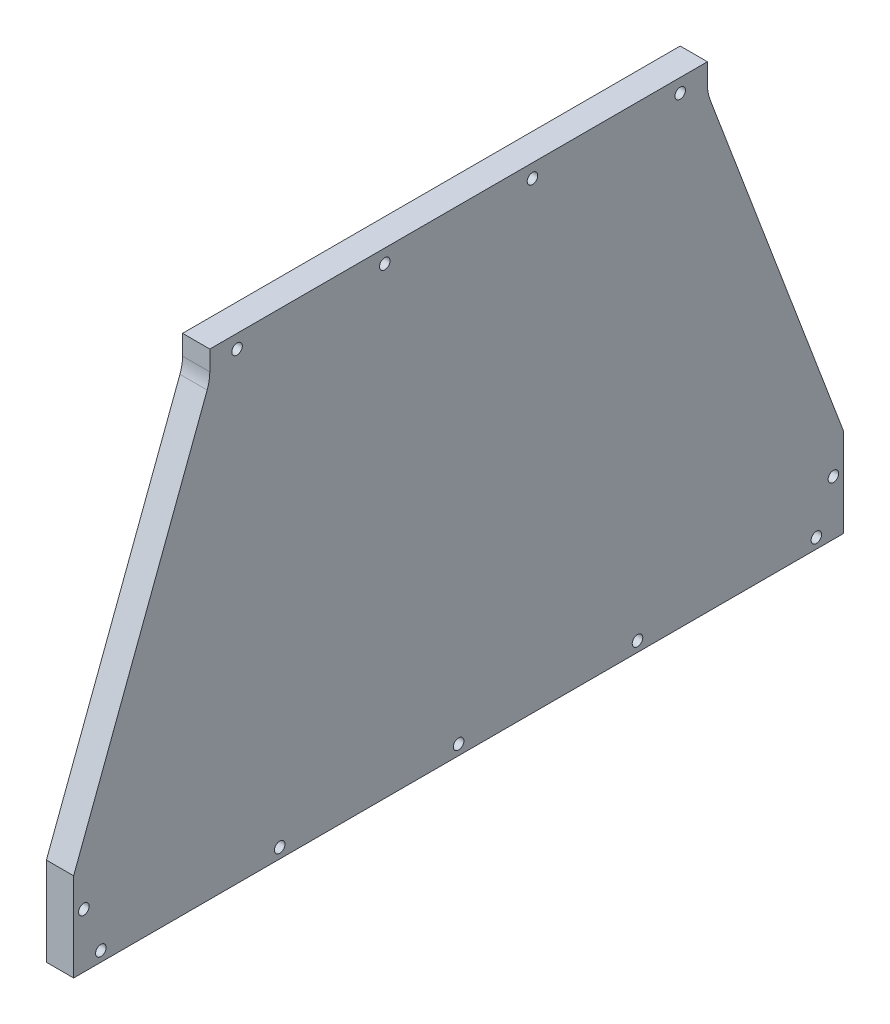
SolidWorks part; units mm, degrees
material "PC High Viscosity"
ref_plane "Front Plane" through (0, 0, 0) normal (0, 0, 1) x (1, 0, 0)
ref_plane "Top Plane" through (0, 0, 0) normal (0, 1, 0) x (1, 0, 0)
ref_plane "Right Plane" through (0, 0, 0) normal (1, 0, 0) x (0, 0, -1)
sketch "Sketch1" plane through (-152.4, 0, 0) normal (-1, 0, 0) x (0, 0, 1)
  line L2 (179.525, -30.525) -> (179.525, 10.75)
  line L3 (179.525, 10.75) -> (116.025, 179.025)
  line L4 (116.025, 179.025) -> (-116.025, 179.025) construction
  line L5 (-116.025, 179.025) -> (-179.525, 10.75)
  line L9 (-116.025, 179.025) -> (-116.025, 191.725)
  line L10 (-116.025, 191.725) -> (116.025, 191.725)
  line L11 (116.025, 191.725) -> (116.025, 179.025)
  line L12 (71.3064, 110.2997) -> (71.3064, 107.6694)
  line L13 (71.3064, 110.2997) -> (71.3064, 107.6694) construction
  line L14 (71.3064, 107.6694) -> (83.0865, 85.1176)
  line L15 (71.3064, 107.6694) -> (83.0865, 85.1176) construction
  line L16 (83.0865, 85.1176) -> (85.1422, 81.1821)
  line L17 (83.0865, 85.1176) -> (85.1422, 81.1821) construction
  line L18 (88.7026, 79.025) -> (105.7742, 79.025)
  line L19 (88.7026, 79.025) -> (105.7742, 79.025) construction
  line L20 (105.7742, 55.4812) -> (88.7026, 55.4812)
  line L21 (105.7742, 55.4812) -> (88.7026, 55.4812) construction
  line L22 (85.1422, 53.3241) -> (83.0865, 49.3886)
  line L23 (85.1422, 53.3241) -> (83.0865, 49.3886) construction
  line L24 (83.0865, 49.3886) -> (71.3064, 26.8368)
  line L25 (83.0865, 49.3886) -> (71.3064, 26.8368) construction
  line L26 (71.3064, 26.8368) -> (71.3064, 24.2065)
  line L27 (71.3064, 26.8368) -> (71.3064, 24.2065) construction
  line L28 (66.4936, 18.7481) -> (34.9092, 18.7481)
  line L29 (66.4936, 18.7481) -> (34.9092, 18.7481) construction
  line L30 (34.9092, 18.7481) -> (32.2596, 20.2319)
  line L31 (34.9092, 18.7481) -> (32.2596, 20.2319) construction
  line L32 (32.2596, 20.2319) -> (24.473, 20.2319)
  line L33 (32.2596, 20.2319) -> (24.473, 20.2319) construction
  line L34 (24.473, 20.2319) -> (24.473, 19.2124)
  line L35 (24.473, 20.2319) -> (24.473, 19.2124) construction
  line L36 (24.473, 19.2124) -> (-24.6855, 19.2124)
  line L37 (24.473, 19.2124) -> (-24.6855, 19.2124) construction
  line L38 (-24.6855, 19.2124) -> (-26.36, 20.1501)
  line L39 (-24.6855, 19.2124) -> (-26.36, 20.1501) construction
  line L40 (-26.36, 20.1501) -> (-48.784, 20.1501)
  line L41 (-26.36, 20.1501) -> (-48.784, 20.1501) construction
  line L42 (-48.784, 20.1501) -> (-58.9234, 27.7663)
  line L43 (-48.784, 20.1501) -> (-58.9234, 27.7663) construction
  line L44 (-58.9234, 27.7663) -> (-60.282, 27.7663)
  line L45 (-58.9234, 27.7663) -> (-60.282, 27.7663) construction
  line L46 (-60.282, 27.7663) -> (-60.4466, 33.2204)
  line L47 (-60.282, 27.7663) -> (-60.4466, 33.2204) construction
  line L48 (-60.4466, 33.2204) -> (-66.7945, 33.2204)
  line L49 (-60.4466, 33.2204) -> (-66.7945, 33.2204) construction
  line L50 (-66.7945, 33.2204) -> (-66.7945, 34.9391)
  line L51 (-66.7945, 33.2204) -> (-66.7945, 34.9391) construction
  line L52 (-109.7529, 42.6097) -> (-109.7529, 91.8965)
  line L53 (-109.7529, 42.6097) -> (-109.7529, 91.8965) construction
  line L54 (-66.7945, 99.5665) -> (-66.7945, 101.2858)
  line L55 (-66.7945, 99.5665) -> (-66.7945, 101.2858) construction
  line L56 (-66.7945, 101.2858) -> (-60.4466, 101.2858)
  line L57 (-66.7945, 101.2858) -> (-60.4466, 101.2858) construction
  line L58 (-60.4466, 101.2858) -> (-60.282, 106.7399)
  line L59 (-60.4466, 101.2858) -> (-60.282, 106.7399) construction
  line L60 (-60.282, 106.7399) -> (-58.9234, 106.7399)
  line L61 (-60.282, 106.7399) -> (-58.9234, 106.7399) construction
  line L62 (-58.9234, 106.7399) -> (-48.784, 114.3561)
  line L63 (-58.9234, 106.7399) -> (-48.784, 114.3561) construction
  line L64 (-48.784, 114.3561) -> (-26.36, 114.3561)
  line L65 (-48.784, 114.3561) -> (-26.36, 114.3561) construction
  line L66 (-26.36, 114.3561) -> (-24.6855, 115.2938)
  line L67 (-26.36, 114.3561) -> (-24.6855, 115.2938) construction
  line L68 (-24.6855, 115.2938) -> (24.473, 115.2938)
  line L69 (-24.6855, 115.2938) -> (24.473, 115.2938) construction
  line L70 (24.473, 115.2938) -> (24.473, 114.2743)
  line L71 (24.473, 115.2938) -> (24.473, 114.2743) construction
  line L72 (24.473, 114.2743) -> (32.2596, 114.2743)
  line L73 (24.473, 114.2743) -> (32.2596, 114.2743) construction
  line L74 (32.2596, 114.2743) -> (34.9092, 115.7581)
  line L75 (32.2596, 114.2743) -> (34.9092, 115.7581) construction
  line L76 (34.9092, 115.7581) -> (66.4936, 115.7581)
  line L77 (34.9092, 115.7581) -> (66.4936, 115.7581) construction
  line L79 (179.525, -30.525) -> (-179.525, -30.525) construction
  line L80 (179.525, -30.525) -> (-179.525, -30.525)
  line L81 (-179.525, -30.525) -> (-179.525, 10.75)
  arc A0 (85.1422, 81.1821) -> (88.7026, 79.025) centre (88.7026, 83.0419) ccw
  arc A1 (85.1422, 81.1821) -> (88.7026, 79.025) centre (88.7026, 83.0419) ccw construction
  arc A2 (108.4945, 77.1118) -> (105.7742, 79.025) centre (105.7742, 76.1345) ccw
  arc A3 (108.4945, 77.1118) -> (105.7742, 79.025) centre (105.7742, 76.1345) ccw construction
  arc A4 (108.4945, 57.3944) -> (108.4945, 77.1118) centre (81.0531, 67.2531) ccw
  arc A5 (108.4945, 57.3944) -> (108.4945, 77.1118) centre (81.0531, 67.2531) ccw construction
  arc A6 (105.7742, 55.4812) -> (108.4945, 57.3944) centre (105.7742, 58.3717) ccw
  arc A7 (105.7742, 55.4812) -> (108.4945, 57.3944) centre (105.7742, 58.3717) ccw construction
  arc A8 (88.7026, 55.4812) -> (85.1422, 53.3241) centre (88.7026, 51.4644) ccw
  arc A9 (88.7026, 55.4812) -> (85.1422, 53.3241) centre (88.7026, 51.4644) ccw construction
  arc A10 (66.4936, 18.7481) -> (71.3064, 24.2065) centre (65.8047, 24.2065) ccw
  arc A11 (66.4936, 18.7481) -> (71.3064, 24.2065) centre (65.8047, 24.2065) ccw construction
  arc A12 (71.3064, 110.2997) -> (66.4936, 115.7581) centre (65.8047, 110.2997) ccw
  arc A13 (71.3064, 110.2997) -> (66.4936, 115.7581) centre (65.8047, 110.2997) ccw construction
  spline S0 degree 3 poles (-4.313, -1962.4963) (19.5421, 71.4299) (-25.3598, 33.5673) (-69.9826, 35.0151) (-72.2561, 35.1637) (-74.9774, 35.4287) (-80.4046, 36.0971) (-247.0965, 65.1595) (-376.3581, 268.4403) (-855.0908, -1792.3669) knots -2.937522 -2.937522 -2.937522 -2.937522 0.03125 0.0625 0.125 0.1875 0.25 0.5 11.786531 11.786531 11.786531 11.786531 only from (-66.7945, 34.9391) to (-109.7529, 42.6097)
  spline S1 degree 3 poles (-66.7945, 34.9391) (-67.2501, 34.9435) (-68.1613, 34.956) (-69.9826, 35.0151) (-72.2561, 35.1637) (-74.9774, 35.4287) (-80.4046, 36.0971) (-92.0812, 38.1329) (-102.7052, 40.749) (-109.7529, 42.6097) knots 0 0 0 0 0.03125 0.0625 0.125 0.1875 0.25 0.5 1 1 1 1 construction
  spline S2 degree 3 poles (-855.0104, 1926.8665) (-376.3436, -133.9191) (-247.0872, 69.3486) (-80.4046, 98.4091) (-74.9775, 99.0775) (-72.2562, 99.3426) (-69.9826, 99.4913) (-25.4887, 100.9281) (19.281, 62.7855) (-4.2393, 2096.9342) knots -10.785888 -10.785888 -10.785888 -10.785888 0.499999 0.749999 0.812499 0.875 0.9375 0.96875 3.928669 3.928669 3.928669 3.928669 only from (-109.7529, 91.8965) to (-66.7945, 99.5665)
  spline S3 degree 3 poles (-109.7529, 91.8965) (-102.7052, 93.7572) (-92.0812, 96.3733) (-80.4046, 98.4091) (-74.9775, 99.0775) (-72.2562, 99.3426) (-69.9826, 99.4913) (-68.1613, 99.5501) (-67.2501, 99.5623) (-66.7945, 99.5665) knots 0 0 0 0 0.499999 0.749999 0.812499 0.875 0.9375 0.96875 1 1 1 1 construction
  dimension "D1" = 12.7
  dimension "D2" = 222.25
  dimension "D3" = 63.5
  dimension "D4" = 41.275
  dimension "D5" = 63.7312
extrude "Boss-Extrude1" add sketch "Sketch1" along normal blind 12.7
fillet "Fillet1" radius 19.05 2 edges at (-158.75, 179.025, -116.025) (-158.75, 179.025, 116.025)
hole_wizard "#10 (0.1935) Diameter Hole1" positions "Sketch2" profile "Sketch3" hole size "#10" standard "ANSI Inch" end condition through all
sketch "Sketch2" plane through (-165.1, 0, 0) normal (-1, 0, 0) x (0, 0, 1)
  line L1 (-103.325, 185.375) -> (-34.4417, 185.375) construction
  line L2 (-34.4417, 185.375) -> (34.4417, 185.375) construction
  line L3 (34.4417, 185.375) -> (103.325, 185.375) construction
  line L5 (166.825, -25.7625) -> (83.4125, -25.7625) construction
  line L6 (83.4125, -25.7625) -> (0, -25.7625) construction
  line L7 (0, -25.7625) -> (-83.4125, -25.7625) construction
  line L8 (-83.4125, -25.7625) -> (-166.825, -25.7625) construction
  line L10 (116.025, 191.725) -> (-116.025, 191.725) construction
  line L11 (-116.025, 191.725) -> (-116.025, 182.4998) construction
  line L12 (116.025, 182.4998) -> (116.025, 191.725) construction
  line L13 (-179.525, -30.525) -> (179.525, -30.525) construction
  line L14 (-179.525, 10.75) -> (-179.525, -30.525) construction
  line L15 (179.525, -30.525) -> (179.525, 10.75) construction
  line L16 (-179.525, 10.75) -> (-179.525, -21) construction
  line L17 (-179.525, 10.75) -> (-179.525, -21) construction
  line L18 (179.525, 10.75) -> (179.525, -21) construction
  line L19 (179.525, 10.75) -> (179.525, -21) construction
  point P0 (-103.325, 185.375)
  point P2 (-34.4417, 185.375)
  point P4 (34.4417, 185.375)
  point P6 (103.325, 185.375)
  point P8 (174.7625, -5.125)
  point P10 (-174.7625, -5.125)
  point P12 (-166.825, -25.7625)
  point P14 (166.825, -25.7625)
  point P16 (0, -25.7625)
  point P18 (83.4125, -25.7625)
  point P20 (-83.4125, -25.7625)
  point P50 (-179.525, -5.125)
  dimension "D1" = 6.35
  dimension "D2" = 12.7
  dimension "D3" = 12.7
  dimension "D4" = 4.7625
  dimension "D5" = 12.7
  dimension "D6" = 12.7
  dimension "D7" = 4.7625
  dimension "D8" = 4.7625
sketch "Sketch3" plane through (-165.1, 185.375, -103.325) normal (0, 1, 0) x (0, 0, 1)
  line L0 (0, 0) -> (0, 12.7)
  line L1 (0, 12.7) -> (2.4574, 12.7)
  line L2 (2.4574, 12.7) -> (2.4574, 0)
  line L5 (2.4574, 0) -> (0, 0)
  line L11 (0, -6.35) -> (0, 107.95) construction
  dimension "Thru Hole Dia." = 4.9149
  dimension "Thru Hole Depth" = 12.7
equation "\"D3@Sketch2\"=\"D2@Sketch2\""
equation "\"D6@Sketch2\"=\"D5@Sketch2\""
equation "\"D8@Sketch2\"=\"D7@Sketch2\""
